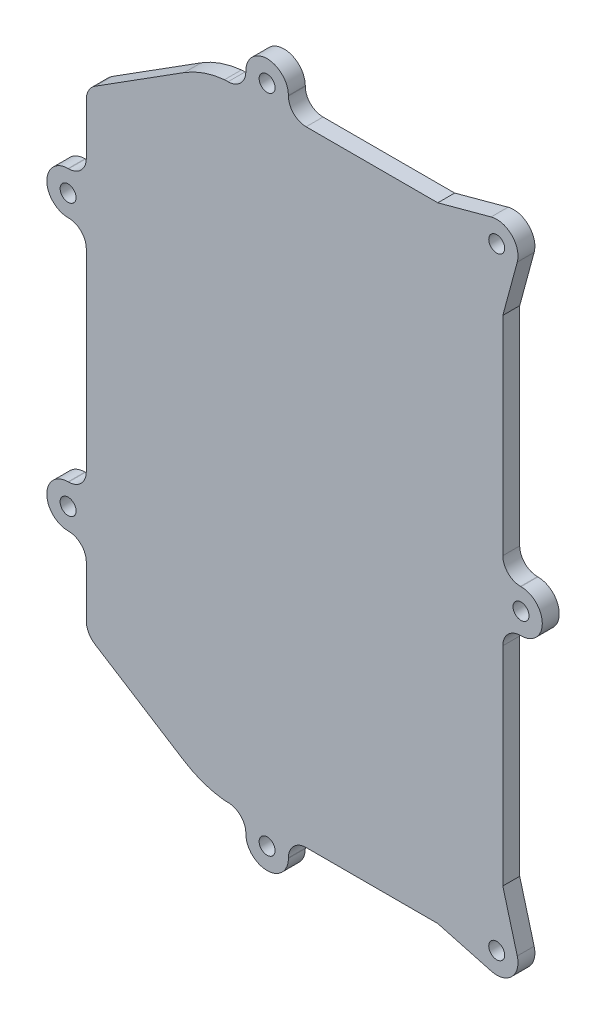
SolidWorks part; units mm, degrees
material "Acrylic (Medium-high impact)"
ref_plane "X-Y Datum" through (0, 0, 0) normal (0, 0, 1) x (1, 0, 0)
ref_plane "X-Z Datum" through (0, 0, 0) normal (0, 1, 0) x (1, 0, 0)
ref_plane "Y-Z Datum" through (0, 0, 0) normal (1, 0, 0) x (0, 0, -1)
sketch "Sketch1" plane through (0, 0, 0) normal (0, 0, 1) x (1, 0, 0)
  line L19 (-106.928, 20.7908) -> (-81.7895, 4.8904)
  line L20 (-114.5434, 44.6987) -> (-114.4107, 44.6987)
  line L21 (-114.4107, 56.6987) -> (-114.5434, 56.6987)
  line L22 (-106.928, 20.7908) -> (-81.7895, 4.8904)
  line L23 (-114.5434, 121.1941) -> (-114.4107, 121.1941)
  line L24 (-114.4107, 133.1941) -> (-114.5434, 133.1941)
  line L25 (-109.4107, 39.6987) -> (-109.4107, 25.2987)
  line L26 (-109.4107, 39.6987) -> (-109.4107, 25.2987)
  line L27 (-69.4289, 176.9464) -> (-70.4289, 176.9464)
  line L28 (-10.3047, 176.9464) -> (-47.4289, 176.9464)
  line L31 (4.7411, 181.017) -> (-10.3047, 176.9464)
  line L33 (8.0293, 158.6124) -> (12.0998, 173.6583)
  line L35 (8.0293, 99.9464) -> (8.0293, 158.6124)
  line L36 (8.0293, 19.2804) -> (8.0293, 77.9464)
  line L38 (12.0998, 4.2346) -> (8.0293, 19.2804)
  line L39 (-10.3047, 0.9464) -> (4.7411, -3.1241)
  line L40 (-47.4289, 0.9464) -> (-10.3047, 0.9464)
  line L42 (-70.4289, 0.9464) -> (-69.4289, 0.9464)
  line L43 (-109.4107, 116.1941) -> (-109.4107, 61.6987)
  line L95 (-114.5434, 44.6987) -> (-114.4107, 44.6987)
  line L96 (-114.4107, 56.6987) -> (-114.5434, 56.6987)
  line L98 (-114.5434, 121.1941) -> (-114.4107, 121.1941)
  line L99 (-114.4107, 133.1941) -> (-114.5434, 133.1941)
  line L102 (-69.4289, 176.9464) -> (-70.4289, 176.9464)
  line L103 (-10.3047, 176.9464) -> (-47.4289, 176.9464)
  line L104 (4.7411, 181.017) -> (-10.3047, 176.9464)
  line L105 (8.0293, 158.6124) -> (12.0998, 173.6583)
  line L106 (8.0293, 99.9464) -> (8.0293, 158.6124)
  line L107 (8.0293, 19.2804) -> (8.0293, 77.9464)
  line L108 (12.0998, 4.2346) -> (8.0293, 19.2804)
  line L109 (-10.3047, 0.9464) -> (4.7411, -3.1241)
  line L110 (-47.4289, 0.9464) -> (-10.3047, 0.9464)
  line L111 (-70.4289, 0.9464) -> (-69.4289, 0.9464)
  line L144 (-109.4107, 116.1941) -> (-109.4107, 61.6987)
  line L145 (-109.4107, 152.5941) -> (-109.4107, 138.1941)
  line L146 (-109.4107, 152.5941) -> (-109.4107, 138.1941)
  line L147 (-81.7895, 173.0025) -> (-106.928, 157.1021)
  line L148 (-81.7895, 173.0025) -> (-106.928, 157.1021)
  line L149 (-64.4289, 182.0791) -> (-64.4289, 181.9464)
  line L150 (-64.4289, 182.0791) -> (-64.4289, 181.9464)
  line L151 (-52.4289, 181.9464) -> (-52.4289, 182.0791)
  line L152 (-52.4289, 181.9464) -> (-52.4289, 182.0791)
  line L153 (13.162, 94.9464) -> (13.0293, 94.9464)
  line L154 (13.162, 94.9464) -> (13.0293, 94.9464)
  line L155 (13.0293, 82.9464) -> (13.162, 82.9464)
  line L156 (13.0293, 82.9464) -> (13.162, 82.9464)
  line L157 (-52.4289, -4.1863) -> (-52.4289, -4.0536)
  line L158 (-52.4289, -4.1863) -> (-52.4289, -4.0536)
  line L159 (-64.4289, -4.0536) -> (-64.4289, -4.1863)
  line L160 (-64.4289, -4.0536) -> (-64.4289, -4.1863)
  arc A21 (-109.4107, 25.2987) -> (-106.928, 20.7908) centre (-104.0767, 25.2987) ccw
  arc A22 (-114.5434, 56.6987) -> (-114.5434, 44.6987) centre (-114.5434, 50.6987) ccw
  arc A23 (-109.4107, 25.2987) -> (-106.928, 20.7908) centre (-104.0767, 25.2987) ccw
  arc A24 (-109.4107, 39.6987) -> (-114.4107, 44.6987) centre (-114.4107, 39.6987) ccw
  arc A25 (-114.5434, 133.1941) -> (-114.5434, 121.1941) centre (-114.5434, 127.1941) ccw
  arc A26 (-109.4107, 39.6987) -> (-114.4107, 44.6987) centre (-114.4107, 39.6987) ccw
  arc A27 (-114.4107, 56.6987) -> (-109.4107, 61.6987) centre (-114.4107, 61.6987) ccw
  arc A63 (-114.4107, 56.6987) -> (-109.4107, 61.6987) centre (-114.4107, 61.6987) ccw
  arc A64 (-69.4289, 176.9464) -> (-64.4289, 181.9464) centre (-69.4289, 181.9464) ccw
  arc A65 (-52.4289, 182.0791) -> (-64.4289, 182.0791) centre (-58.4289, 182.0791) ccw
  arc A66 (-52.4289, 181.9464) -> (-47.4289, 176.9464) centre (-47.4289, 181.9464) ccw
  arc A67 (12.0998, 173.6583) -> (4.7411, 181.017) centre (6.3081, 175.2252) ccw
  arc A68 (8.0293, 99.9464) -> (13.0293, 94.9464) centre (13.0293, 99.9464) ccw
  arc A69 (13.162, 82.9464) -> (13.162, 94.9464) centre (13.162, 88.9464) ccw
  arc A70 (13.0293, 82.9464) -> (8.0293, 77.9464) centre (13.0293, 77.9464) ccw
  arc A72 (4.7411, -3.1241) -> (12.0998, 4.2346) centre (6.3081, 2.6677) ccw
  arc A74 (-47.4289, 0.9464) -> (-52.4289, -4.0536) centre (-47.4289, -4.0536) ccw
  arc A76 (-64.4289, -4.1863) -> (-52.4289, -4.1863) centre (-58.4289, -4.1863) ccw
  arc A79 (-64.4289, -4.0536) -> (-69.4289, 0.9464) centre (-69.4289, -4.0536) ccw
  arc A83 (-109.4107, 116.1941) -> (-114.4107, 121.1941) centre (-114.4107, 116.1941) ccw
  arc A87 (-109.4107, 116.1941) -> (-114.4107, 121.1941) centre (-114.4107, 116.1941) ccw
  arc A95 (-114.5434, 56.6987) -> (-114.5434, 44.6987) centre (-114.5434, 50.6987) ccw
  arc A123 (-114.5434, 133.1941) -> (-114.5434, 121.1941) centre (-114.5434, 127.1941) ccw
  arc A127 (-69.4289, 176.9464) -> (-64.4289, 181.9464) centre (-69.4289, 181.9464) ccw
  arc A128 (-52.4289, 182.0791) -> (-64.4289, 182.0791) centre (-58.4289, 182.0791) ccw
  arc A129 (-52.4289, 181.9464) -> (-47.4289, 176.9464) centre (-47.4289, 181.9464) ccw
  arc A130 (12.0998, 173.6583) -> (4.7411, 181.017) centre (6.3081, 175.2252) ccw
  arc A131 (8.0293, 99.9464) -> (13.0293, 94.9464) centre (13.0293, 99.9464) ccw
  arc A132 (13.162, 82.9464) -> (13.162, 94.9464) centre (13.162, 88.9464) ccw
  arc A133 (13.0293, 82.9464) -> (8.0293, 77.9464) centre (13.0293, 77.9464) ccw
  arc A134 (4.7411, -3.1241) -> (12.0998, 4.2346) centre (6.3081, 2.6677) ccw
  arc A135 (-47.4289, 0.9464) -> (-52.4289, -4.0536) centre (-47.4289, -4.0536) ccw
  arc A136 (-64.4289, -4.1863) -> (-52.4289, -4.1863) centre (-58.4289, -4.1863) ccw
  arc A137 (-64.4289, -4.0536) -> (-69.4289, 0.9464) centre (-69.4289, -4.0536) ccw
  arc A161 (-114.4107, 133.1941) -> (-109.4107, 138.1941) centre (-114.4107, 138.1941) ccw
  arc A162 (-114.4107, 133.1941) -> (-109.4107, 138.1941) centre (-114.4107, 138.1941) ccw
  arc A163 (-106.928, 157.1021) -> (-109.4107, 152.5941) centre (-104.0767, 152.5941) ccw
  arc A164 (-106.928, 157.1021) -> (-109.4107, 152.5941) centre (-104.0767, 152.5941) ccw
  arc A165 (-70.4289, 176.9464) -> (-81.7895, 173.0025) centre (-67.681, 150.6969) ccw
  arc A166 (-70.4289, 176.9464) -> (-81.7895, 173.0025) centre (-67.681, 150.6969) ccw
  arc A167 (-81.7895, 4.8904) -> (-70.4289, 0.9464) centre (-67.681, 27.196) ccw
  arc A168 (-81.7895, 4.8904) -> (-70.4289, 0.9464) centre (-67.681, 27.196) ccw
  dimension "D1" = 0
extrude "Boss-Extrude1" add sketch "Sketch1" against normal blind 4.7625
hole_wizard "M4 Clearance Hole1" positions "Sketch2" profile "Sketch3" hole size "M4" standard "ANSI Metric" end condition through all
sketch "Sketch2" plane through (0, 0, -4.7625) normal (0, 0, -1) x (-1, 0, 0)
  point P0 (-6.3081, 175.2252)
  point P3 (-13.162, 88.9464)
  point P6 (-6.3081, 2.6677)
  point P11 (114.5434, 50.6987)
  point P14 (114.5434, 127.1941)
  point P17 (58.4289, 182.0791)
  point P22 (58.4289, -4.1863)
sketch "Sketch3" plane through (6.3081, 175.2252, -4.7625) normal (1, 0, 0) x (0, 1, 0)
  line L0 (0, 0) -> (0, 4.7625)
  line L1 (0, 4.7625) -> (2.25, 4.7625)
  line L2 (2.25, 4.7625) -> (2.25, 0)
  line L5 (2.25, 0) -> (0, 0)
  line L11 (0, -6.35) -> (0, 107.95) construction
  dimension "Thru Hole Dia." = 4.5
  dimension "Thru Hole Depth" = 4.7625
